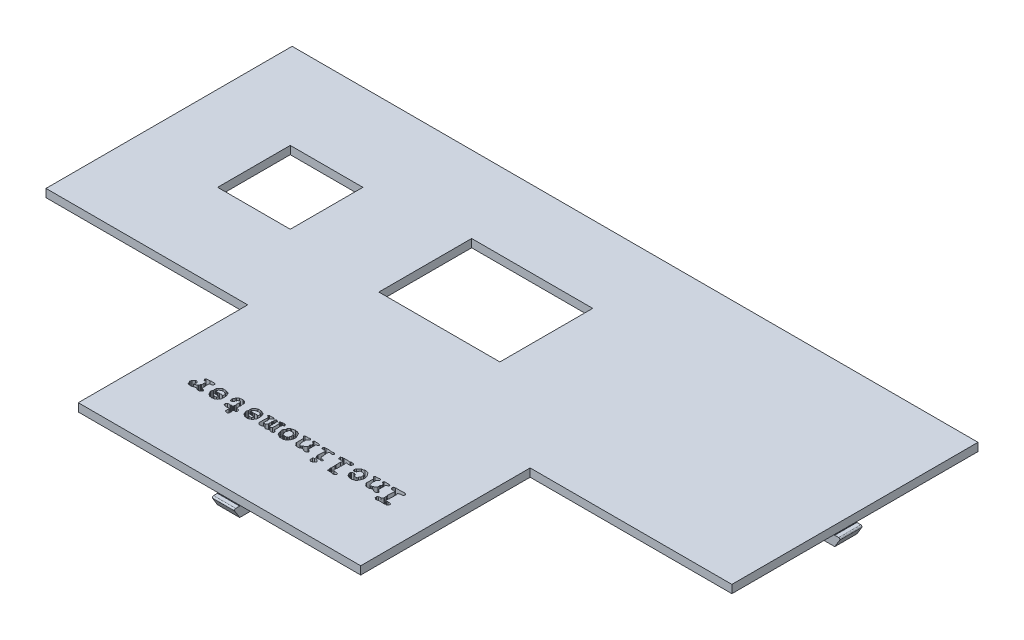
SolidWorks part; units mm, degrees
ref_plane "Front Plane" through (0, 0, 0) normal (0, 0, 1) x (1, 0, 0)
ref_plane "Top Plane" through (0, 0, 0) normal (0, 1, 0) x (1, 0, 0)
ref_plane "Right Plane" through (0, 0, 0) normal (1, 0, 0) x (0, 0, -1)
sketch "Sketch1" plane through (0, 0, 0) normal (0, 1, 0) x (1, 0, 0)
  line L0 (40.4395, 0.2372) -> (90.4395, 0.2372)
  line L1 (-79.5605, 61.2372) -> (90.4395, 61.2372)
  line L2 (-79.5605, 61.2372) -> (-79.5605, 0.2372)
  line L3 (-79.5605, 0.2372) -> (-29.5605, 0.2372)
  line L4 (90.4395, 61.2372) -> (90.4395, 0.2372)
  line L10 (-29.5605, 0.2372) -> (-29.5605, -41.7628)
  line L11 (-29.5605, -41.7628) -> (40.4395, -41.7628)
  line L12 (40.4395, 0.2372) -> (40.4395, -41.7628)
  line L13 (-29.5605, 0.2372) -> (40.4395, -41.7628) construction
  line L14 (-29.5605, -41.7628) -> (40.4395, 0.2372) construction
  point P4 (5.4395, -20.7628)
  dimension "D1" = 170
  dimension "D2" = 61
  dimension "D3" = 70
  dimension "D4" = 42
  dimension "D5" = 42
extrude "Boss-Extrude1" add sketch "Sketch1" along normal blind 2 contours L10 L11 L12 L0 L4 L1 L2 L3
sketch "Sketch2" plane through (0, 0, 0) normal (0, -1, 0) x (1, 0, 0)
  line L0 (90.4395, -61.2372) -> (90.4395, -0.2372) construction
  line L1 (88.1895, -27.9763) -> (85.6895, -27.9763)
  line L2 (88.1895, -27.9763) -> (88.1895, -33.4763)
  line L3 (88.1895, -33.4763) -> (85.6895, -33.4763)
  line L4 (85.6895, -27.9763) -> (85.6895, -33.4763)
  line L7 (90.4395, -30.7372) -> (82.2542, -30.7372) construction
  dimension "D1" = 5.5
  dimension "D2" = 2.5
  dimension "D3" = 2.25
extrude "Boss-Extrude2" add sketch "Sketch2" along normal blind 4.9
sketch "Sketch4" plane through (0, 0, -33.4763) normal (0, 0, -1) x (-1, 0, 0)
  line L0 (-88.1895, -4.9) -> (-88.1895, -2.45)
  line L1 (-88.1895, -4.9) -> (-88.1895, 0) construction
  line L2 (-88.1895, -2.45) -> (-89.6895, -2.45)
  line L3 (-89.6895, -2.45) -> (-88.1895, -4.9)
extrude "Boss-Extrude3" add sketch "Sketch4" against normal up to surface (5.5 mm away) up to face at (86.9395, -2.45, -27.9763)
fillet "Fillet1" radius 0.3 1 edges at (89.6895, -2.45, -30.7263)
sketch "Sketch5" plane through (0, 0, 0) normal (0, -1, 0) x (1, 0, 0)
  line L0 (5.4395, -61.2372) -> (5.4395, 41.7628)
  line L1 (-79.5605, -61.2372) -> (90.4395, -61.2372) construction
  line L2 (-29.5605, 41.7628) -> (40.4395, 41.7628) construction
  line L3 (5.4395, -61.2372) -> (4.4275, -61.2372)
  line L4 (4.4275, -61.2372) -> (4.4275, 41.7628)
  line L5 (4.4275, 41.7628) -> (5.4395, 41.7628)
extrude "Boss-Extrude4" add sketch "Sketch5" along normal blind 0.1 contours L4 L5 L0 L3
mirror "Mirror2" about plane through (5.4395, -0.1, -61.2372) normal (-1, 0, 0) of "Boss-Extrude2", "Boss-Extrude3"
fillet "Fillet2" radius 0.3 1 edges at (-78.8105, -2.45, -30.7263)
sketch "Sketch6" plane through (0, 0, 0) normal (0, -1, 0) x (1, 0, 0)
  line L0 (-79.5605, -61.2372) -> (4.4275, -61.2372) construction
  line L1 (-33.8105, -58.9872) -> (-39.3105, -58.9872)
  line L2 (-33.8105, -58.9872) -> (-33.8105, -56.4872)
  line L3 (-33.8105, -56.4872) -> (-39.3105, -56.4872)
  line L4 (-39.3105, -58.9872) -> (-39.3105, -56.4872)
  line L5 (-79.5605, -61.2372) -> (-79.5605, -0.2372) construction
  dimension "D1" = 2.5
  dimension "D2" = 5.5
  dimension "D3" = 2.25
  dimension "D4" = 40.25
extrude "Boss-Extrude5" add sketch "Sketch6" along normal blind 4.9 contours L3 L4 L1 L2
sketch "Sketch9" plane through (-39.3105, 0, 0) normal (-1, 0, 0) x (0, 0, 1)
  line L0 (-58.9872, -4.9) -> (-58.9872, -2.45)
  line L1 (-58.9872, -4.9) -> (-58.9872, 0) construction
  line L2 (-58.9872, -2.45) -> (-60.4872, -2.45)
  line L3 (-60.4872, -2.45) -> (-58.9872, -4.9)
extrude "Boss-Extrude6" add sketch "Sketch9" against normal up to surface (5.5 mm away) up to face at (-33.8105, -2.45, -57.7372)
fillet "Fillet3" radius 0.3 1 edges at (-36.5605, -2.45, -60.4872)
mirror "Mirror5" about plane through (5.4395, -0.1, -61.2372) normal (-1, 0, 0) of "Fillet3", "Boss-Extrude6", "Boss-Extrude5"
sketch "Sketch10" plane through (0, -0.1, 0) normal (0, -1, 0) x (1, 0, 0)
  line L4 (4.4275, -61.2372) -> (5.4395, -61.2372)
  line L5 (5.4395, -61.2372) -> (5.4395, 41.7628)
  line L6 (5.4395, 41.7628) -> (4.4275, 41.7628)
  line L7 (4.4275, 41.7628) -> (4.4275, -61.2372)
  line L8 (4.4275, -61.2372) -> (5.4395, -61.2372)
  line L9 (5.4395, -61.2372) -> (5.4395, 41.7628)
  line L10 (5.4395, 41.7628) -> (4.4275, 41.7628)
  line L11 (4.4275, 41.7628) -> (4.4275, -61.2372)
  dimension "D1" = 0
extrude "Cut-Extrude1" cut sketch "Sketch10" against normal up to surface (0.1 mm away) up to face at (-76.0605, 0, -30.7263)
sketch "Sketch13" plane through (0, 0, 0) normal (0, -1, 0) x (1, 0, 0)
  line L0 (5.4395, 41.7628) -> (5.4395, 34.9951) construction
  line L1 (-29.5605, 41.7628) -> (40.4395, 41.7628) construction
sketch "Sketch11" plane through (0, 0, 0) normal (0, -1, 0) x (1, 0, 0)
  line L9 (-29.5605, 41.7628) -> (40.4395, 41.7628) construction
  line L10 (8.1895, 37.0128) -> (2.6895, 37.0128)
  line L11 (8.1895, 37.0128) -> (8.1895, 39.5128)
  line L12 (8.1895, 39.5128) -> (2.6895, 39.5128)
  line L13 (2.6895, 37.0128) -> (2.6895, 39.5128)
  line L14 (8.1895, 37.0128) -> (2.6895, 39.5128) construction
  line L15 (8.1895, 39.5128) -> (2.6895, 37.0128) construction
  line L16 (5.4395, 41.7628) -> (5.4395, 34.9951) construction
  point P0 (5.4395, 38.2628)
  dimension "D1" = 2.25
  dimension "D2" = 5.5
  dimension "D3" = 2.5
extrude "Boss-Extrude7" add sketch "Sketch11" along normal blind 4.9 contours L12 L13 L10 L11
sketch "Sketch12" plane through (2.6895, 0, 0) normal (-1, 0, 0) x (0, 0, 1)
  line L0 (39.5128, -4.9) -> (39.5128, -2.45)
  line L1 (39.5128, -4.9) -> (39.5128, 0) construction
  line L2 (39.5128, -2.45) -> (41.0128, -2.45)
  line L3 (41.0128, -2.45) -> (39.5128, -4.9)
extrude "Boss-Extrude8" add sketch "Sketch12" against normal up to surface (5.5 mm away) up to face at (8.1895, -2.45, 38.2628)
fillet "Fillet4" radius 0.3 1 edges at (5.4395, -2.45, 41.0128)
sketch "Sketch14" plane through (0, 2, 0) normal (0, 1, 0) x (1, 0, 0)
  line L0 (-79.5605, 61.2372) -> (90.4395, 61.2372) construction
  line L1 (13.9395, 19.2372) -> (-16.0605, 19.2372)
  line L2 (13.9395, 19.2372) -> (13.9395, 42.2372)
  line L3 (13.9395, 42.2372) -> (-16.0605, 42.2372)
  line L4 (-16.0605, 19.2372) -> (-16.0605, 42.2372)
  line L5 (-40.5205, 21.7372) -> (-58.5205, 21.7372)
  line L6 (-40.5205, 21.7372) -> (-40.5205, 39.7372)
  line L7 (-40.5205, 39.7372) -> (-58.5205, 39.7372)
  line L8 (-58.5205, 21.7372) -> (-58.5205, 39.7372)
  line L9 (-42.5205, 21.9272) -> (-56.5205, 21.9272) construction
  line L10 (-42.5205, 21.9272) -> (-42.5205, 35.9272) construction
  line L11 (-42.5205, 35.9272) -> (-56.5205, 35.9272) construction
  line L12 (-56.5205, 21.9272) -> (-56.5205, 35.9272) construction
  line L13 (10.5195, 18.4672) -> (-15.4805, 18.4672) construction
  line L14 (10.5195, 18.4672) -> (10.5195, 37.4672) construction
  line L15 (10.5195, 37.4672) -> (-15.4805, 37.4672) construction
  line L16 (-15.4805, 18.4672) -> (-15.4805, 37.4672) construction
  line L17 (90.4395, 61.2372) -> (90.4395, 0.2372) construction
  dimension "D1" = 30
  dimension "D2" = 23
  dimension "D3" = 18
  dimension "D4" = 18
  dimension "D5" = 19
  dimension "D6" = 4
  dimension "D7" = 76.5
  dimension "D9" = 21.5
extrude "Cut-Extrude2" cut sketch "Sketch14" against normal blind 10
sketch "Sketch15" plane through (0, 2, 0) normal (0, 1, 0) x (1, 0, 0)
  line L0 (40.4395, -20.7628) -> (-29.5605, -20.7628) construction
  line L1 (40.4395, 0.2372) -> (40.4395, -41.7628) construction
  line L2 (-29.5605, 0.2372) -> (-29.5605, -41.7628) construction
  text T0 "Inclinometer" font "Fixed Typewriter Royal" height 5
extrude "Cut-Extrude3" cut sketch "Sketch15" against normal blind 1.5
